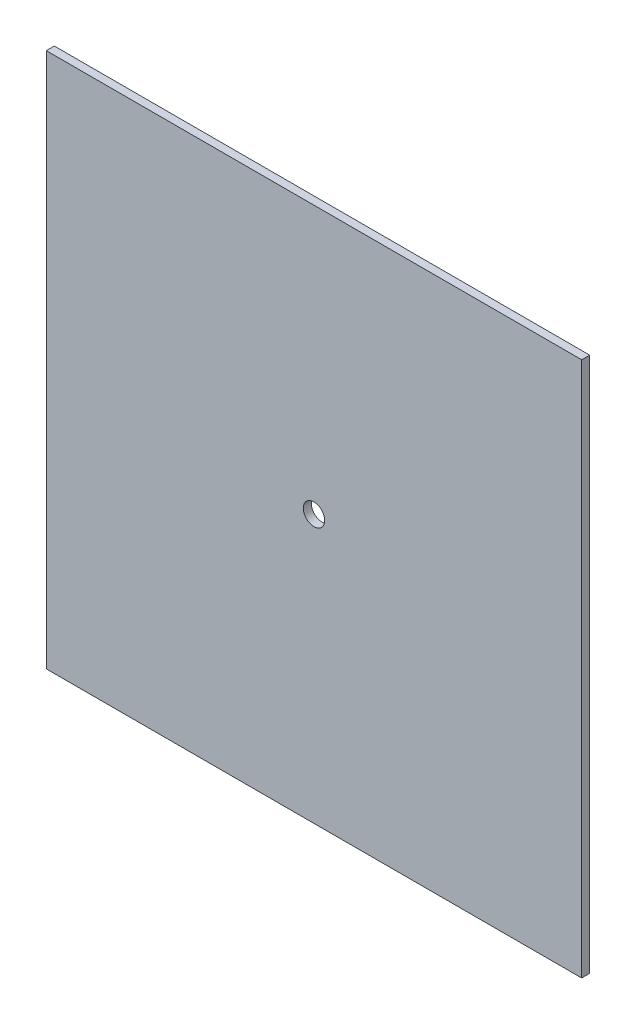
SolidWorks part; units mm, degrees
ref_plane "Front Plane" through (0, 0, 0) normal (0, 0, 1) x (1, 0, 0)
ref_plane "Top Plane" through (0, 0, 0) normal (0, 1, 0) x (1, 0, 0)
ref_plane "Right Plane" through (0, 0, 0) normal (1, 0, 0) x (0, 0, -1)
sketch "Baseplate" plane through (0, 0, 0) normal (0, 0, 1) x (1, 0, 0)
  line L2 (-100, 100) -> (100, 100)
  line L3 (-100, 100) -> (-100, -100)
  line L4 (-100, -100) -> (100, -100)
  line L5 (100, 100) -> (100, -100)
  line L6 (-100, 100) -> (100, -100) construction
  line L7 (-100, -100) -> (100, 100) construction
  point P2 (0, 0)
  dimension "D1" = 200
  dimension "D2" = 200
extrude "Boss-Extrude1" add sketch "Baseplate" along normal blind 3
sketch "Sketch3" plane through (0, 0, 3) normal (0, 0, 1) x (1, 0, 0)
  circle A0 centre (0, 0) radius 4
  point P3 (0, 0)
  dimension "D1" = 8
extrude "Cut-Extrude1" cut sketch "Sketch3" against normal blind 3
